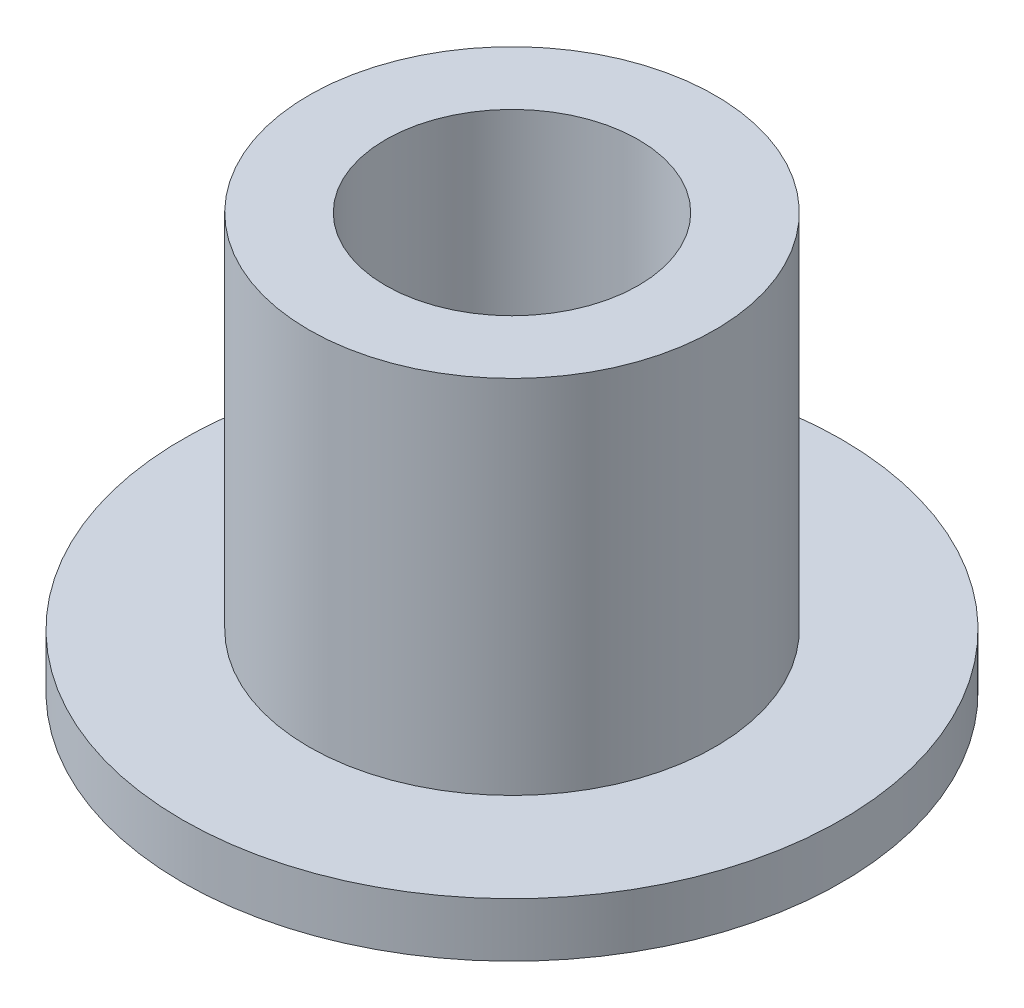
SolidWorks part; units mm, degrees
ref_plane "Front Plane" through (0, 0, 0) normal (0, 0, 1) x (1, 0, 0)
ref_plane "Top Plane" through (0, 0, 0) normal (0, 1, 0) x (1, 0, 0)
ref_plane "Right Plane" through (0, 0, 0) normal (1, 0, 0) x (0, 0, -1)
sketch "Sketch1" plane through (0, 0, 0) normal (0, 1, 0) x (1, 0, 0)
  circle A0 centre (0, 0) radius 14.2875
  circle A1 centre (0, 0) radius 6.35 construction
  circle A2 centre (0, 0) radius 23.1775
  circle A4 centre (0, 0) radius 8.89
  dimension "D1" = 28.575
  dimension "D2" = 12.7
  dimension "D3" = 8.89
  dimension "D4" = 2.54
extrude "Boss-Extrude2" add sketch "Sketch1" against normal blind 3.81 contours A2 A0 region at (-22.5219, 0, 0)
extrude "Boss-Extrude3" add sketch "Sketch1<4>" along normal blind 25.4 and the other way up to surface (3.81 mm away) contours A0 A4 region at (-13.8834, 0, 0) other way up to face at (0, -3.81, 14.2875)
sketch "Sketch1<4>" plane through (0, 0, 0) normal (0, 1, 0) x (1, 0, 0) same geometry as "Sketch1"
